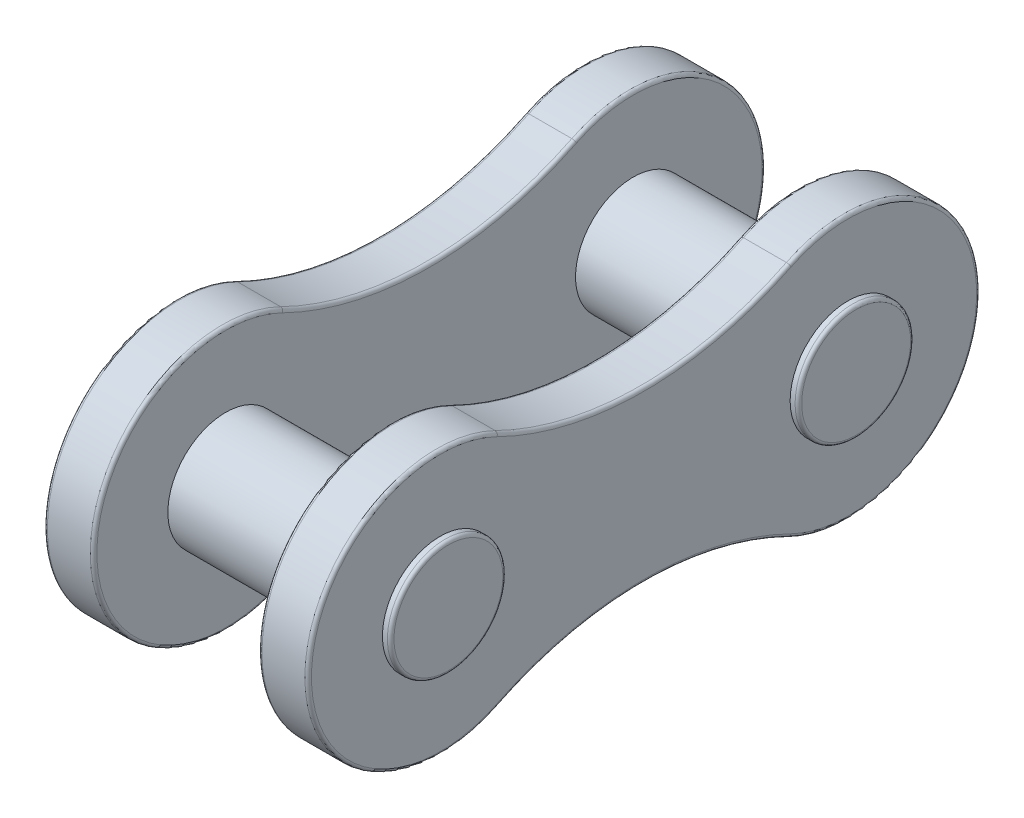
SolidWorks part; units mm, degrees
ref_plane "Front Plane" through (0, 0, 0) normal (0, 0, 1) x (1, 0, 0)
ref_plane "Top Plane" through (0, 0, 0) normal (0, 1, 0) x (1, 0, 0)
ref_plane "Right Plane" through (0, 0, 0) normal (1, 0, 0) x (0, 0, -1)
sketch "Sketch5" plane through (0, 0, 0) normal (1, 0, 0) x (0, 0, -1)
  line L0 (0, -1454.1638) -> (0, 3744.1855) construction
  line L1 (6175, 0) -> (-6175, 0) construction
  arc A0 (-4410.7143, 3589.888) -> (-4410.7143, -3589.888) centre (-6175, 0) ccw
  circle A1 centre (-6175, 0) radius 1750
  circle A2 centre (6175, 0) radius 1750
  arc A3 (4410.7143, 3589.888) -> (4410.7143, -3589.888) centre (6175, 0) cw
  arc A4 (-4410.7143, 3589.888) -> (4410.7143, 3589.888) centre (0, 12564.608) ccw
  arc A5 (-4410.7143, -3589.888) -> (4410.7143, -3589.888) centre (0, -12564.608) cw
  dimension "D1" = 8000
  dimension "D2" = 3500
  dimension "D4" = 10000
  dimension "D3" = 12350
extrude "Boss-Extrude2" add sketch "Sketch5" along normal blind 1500 from offset 2500
sketch "Sketch6" plane through (0, 0, 0) normal (1, 0, 0) x (0, 0, -1)
  circle A0 centre (6175, 0) radius 1750 construction
  circle A1 centre (-6175, 0) radius 1750 construction
  circle A2 centre (6175, 0) radius 1750
  circle A3 centre (-6175, 0) radius 1750
  arc A4 (-4410.7143, 3589.888) -> (4410.7143, 3589.888) centre (0, 12564.608) ccw
  arc A5 (-4410.7143, 3589.888) -> (-4410.7143, -3589.888) centre (-6175, 0) ccw
  arc A6 (4410.7143, -3589.888) -> (-4410.7143, -3589.888) centre (0, -12564.608) ccw
  arc A7 (4410.7143, -3589.888) -> (4410.7143, 3589.888) centre (6175, 0) ccw
  arc A8 (-4410.7143, 3589.888) -> (4410.7143, 3589.888) centre (0, 12564.608) ccw
  arc A9 (-4410.7143, 3589.888) -> (-4410.7143, -3589.888) centre (-6175, 0) ccw
  arc A10 (4410.7143, -3589.888) -> (-4410.7143, -3589.888) centre (0, -12564.608) ccw
  arc A11 (4410.7143, -3589.888) -> (4410.7143, 3589.888) centre (6175, 0) ccw
  dimension "D1" = 0
extrude "Boss-Extrude3" add sketch "Sketch6" against normal blind 1500 from offset 2500 separate body offset against normal yes
sketch "Sketch7" plane through (0, 0, 0) normal (1, 0, 0) x (0, 0, -1)
  circle A0 centre (6175, 0) radius 1750 construction
  circle A1 centre (-6175, 0) radius 1750 construction
  circle A2 centre (6175, 0) radius 1750
  circle A3 centre (-6175, 0) radius 1750
extrude "Boss-Extrude4" add sketch "Sketch7" along normal mid plane 8500
fillet "Fillet1" radius 100 20 edges at (4000, 0, -10175) (4000, -2564.608, 0) (4000, 0, 10175) (2500, 0, -10175) (2500, -2564.608, 0) (2500, 0, 10175) (-4000, 0, -10175) (-4000, -2564.608, 0) (-4000, 0, 10175) (-2500, 0, -10175) (-2500, -2564.608, 0) (-2500, 0, 10175) (4000, 2564.608, 0) (2500, 2564.608, 0) (-4000, 2564.608, 0) (-2500, 2564.608, 0) (-4250, 0, -7925) (-4250, 0, 4425) (4250, 0, -7925) (4250, 0, 4425)
